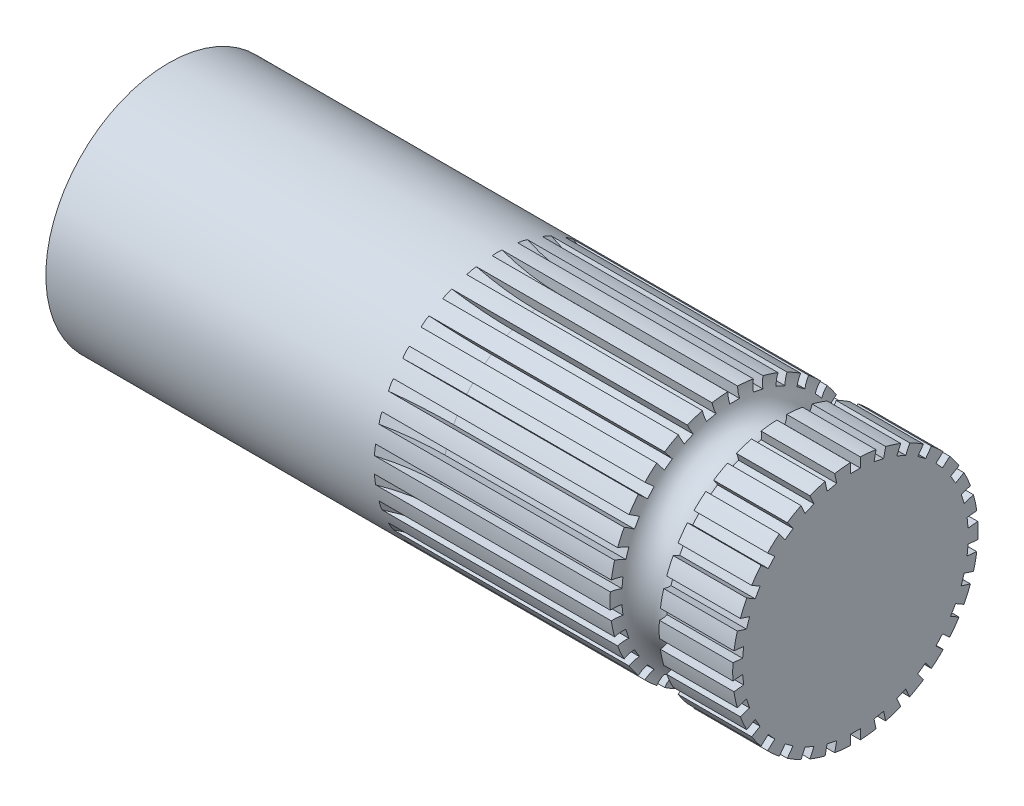
SolidWorks part; units mm, degrees
ref_plane "Front Plane" through (0, 0, 0) normal (0, 0, 1) x (1, 0, 0)
ref_plane "Top Plane" through (0, 0, 0) normal (0, 1, 0) x (1, 0, 0)
ref_plane "Right Plane" through (0, 0, 0) normal (1, 0, 0) x (0, 0, -1)
sketch "Sketch1" plane through (0, 0, 0) normal (0, 0, 1) x (1, 0, 0)
  line L0 (0, 0) -> (0, 12.5)
  line L1 (0, 12.5) -> (70, 12.5)
  line L2 (70, 12.5) -> (70, 0)
  line L3 (70, 0) -> (0, 0)
  line L4 (0, 0) -> (70, 0) construction
  dimension "D1" = 12.5
  dimension "D2" = 70
revolve "Revolve1" add sketch "Sketch1" angle 360 about L4
sketch "Sketch3" plane through (0, 0, 0) normal (0, 0, 1) x (1, 0, 0)
  line L0 (70, 12.5) -> (39.2656, 12.5)
  line L1 (70, 12.5) -> (0, 12.5) construction
  arc A0 (25.02, 20.8392) -> (39.2656, 12.5) centre (39.2656, 28.8372) ccw
sketch "Sketch4" plane through (70, 0, 0) normal (1, 0, 0) x (0, 0, -1)
  line L0 (0, 20.8392) -> (0, 12.5) construction
  line L1 (-0.5, 15.0969) -> (0.5, 15.0969)
  line L2 (-0.5, 15.0969) -> (-0.5, 11.5)
  line L3 (-0.5, 11.5) -> (0.5, 11.5)
  line L4 (0.5, 15.0969) -> (0.5, 11.5)
  dimension "D1" = 1
  dimension "D2" = 0.5
  dimension "D3" = 11.5
sweep "Cut-Sweep1" cut profiles "Sketch4" path "Sketch3"
pattern_circular "CirPattern1" count 30 over 360 about axis through (0, 0, 0) along (-1, 0, 0) of "Cut-Sweep1"
sketch "Sketch5" plane through (0, 0, 0) normal (0, 0, 1) x (1, 0, 0)
  line L0 (0, 0) -> (21.9366, 0) construction
  line L1 (70, 0) -> (0, 0) construction
  line L2 (70, 12.49) -> (33.4909, 12.49) construction
  circle A0 centre (60, 12.49) radius 2.5
  dimension "D1" = 5
  dimension "D2" = 10
revolve "Cut-Revolve1" cut sketch "Sketch5" angle 360 about L0
